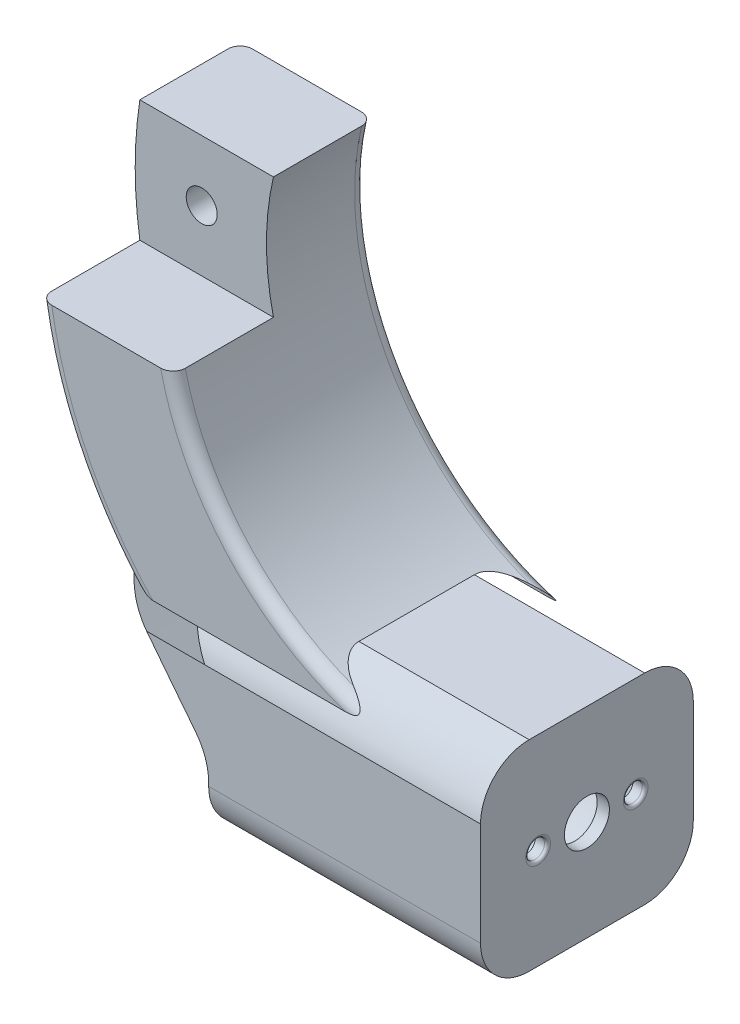
SolidWorks part; units mm, degrees
ref_plane "Front Plane" through (0, 0, 0) normal (0, 0, 1) x (1, 0, 0)
ref_plane "Top Plane" through (0, 0, 0) normal (0, 1, 0) x (1, 0, 0)
ref_plane "Right Plane" through (0, 0, 0) normal (1, 0, 0) x (0, 0, -1)
sketch "Sketch5" plane through (0, 0, -33) normal (0, 0, -1) x (-1, 0, 0)
  line L0 (31.0391, -85.25) -> (64.0391, -85.25)
  line L4 (54.5911, -55.6223) -> (76.5632, -55.6223)
  line L5 (76.5632, -35.6223) -> (54.5911, -35.6223)
  line L7 (76.5632, -35.6223) -> (54.5911, -35.6223)
  arc A0 (54.5911, -55.6223) -> (31.0391, -85.25) centre (11.6, -45.6223) cw
  arc A1 (76.5632, -55.6223) -> (64.0391, -85.25) centre (11.6, -45.6223) cw
  arc A4 (54.5911, -55.6223) -> (54.5911, -35.6223) centre (11.6, -45.6223) ccw
  arc A5 (76.5632, -55.6223) -> (76.5632, -35.6223) centre (11.6, -45.6223) ccw
  arc A6 (54.5911, -55.6223) -> (54.5911, -35.6223) centre (11.6, -45.6223) ccw
  arc A7 (76.5632, -55.6223) -> (76.5632, -35.6223) centre (11.6, -45.6223) ccw
  point P10 (21.6723, -47.1727)
  dimension "D1" = 0
  dimension "D2" = 33
extrude "Boss-Extrude1" add sketch "Sketch5" against normal blind 33
fillet "Fillet1" radius 2 4 edges at (-75.3303, -61.7053, -33) (-75.3303, -61.7053, 0) (-51.4762, -64.5465, 0) (-51.4762, -64.5465, -33)
sketch "Sketch6" plane through (0, 0, -16.5) normal (0, 0, -1) x (-1, 0, 0)
  line L2 (54.5911, -55.6223) -> (76.5632, -55.6223)
  line L3 (76.5632, -35.6223) -> (54.5911, -35.6223)
  line L4 (54.5911, -55.6223) -> (76.5632, -55.6223)
  line L5 (76.5632, -35.6223) -> (54.5911, -35.6223)
  arc A2 (54.5911, -55.6223) -> (54.5911, -35.6223) centre (11.6, -45.6223) ccw
  arc A3 (76.5632, -55.6223) -> (76.5632, -35.6223) centre (11.6, -45.6223) ccw
  arc A4 (54.5911, -55.6223) -> (54.5911, -35.6223) centre (11.6, -45.6223) ccw
  arc A5 (76.5632, -55.6223) -> (76.5632, -35.6223) centre (11.6, -45.6223) ccw
  dimension "D1" = 0
extrude "Cut-Extrude1" cut sketch "Sketch6" against normal through all
sketch "Sketch7" plane through (0, 0, -33) normal (0, 0, -1) x (-1, 0, 0)
  circle A0 centre (66.3894, -45.6223) radius 2.55 construction
  circle A1 centre (66.3894, -45.6223) radius 2.55
extrude "Cut-Extrude2" cut sketch "Sketch7" against normal through all
sketch "Sketch8" plane through (0, -85.25, 0) normal (0, -1, 0) x (1, 0, 0)
  line L0 (-31.0391, -16.5) -> (-64.0391, -16.5) construction
  line L2 (-5.0391, 1) -> (-80.0391, 1)
  line L3 (-5.0391, 1) -> (-5.0391, -34)
  line L4 (-64.0391, -2) -> (-64.0391, -31)
  line L5 (-61.5094, -33) -> (-35.2312, -33)
  line L6 (-31.0391, -31) -> (-31.0391, -2)
  line L7 (-35.2312, 0) -> (-61.5094, 0)
  line L8 (-64.0391, -2) -> (-64.0391, -31) construction
  line L9 (-61.5094, -33) -> (-35.2312, -33) construction
  line L10 (-31.0391, -31) -> (-31.0391, -2) construction
  line L11 (-35.2312, 0) -> (-61.5094, 0) construction
  line L12 (-5.0391, -34) -> (-80.0391, -34)
  line L13 (-80.0391, 1) -> (-80.0391, -34)
  line L14 (-5.0391, 1) -> (-80.0391, -34) construction
  line L15 (-5.0391, -34) -> (-80.0391, 1) construction
  spline S4 degree 3 poles (3861.8063, 733.6796) (237.2103, 60.9029) (-69.0926, -13.3538) (-63.9372, -31.5831) (-63.8768, -31.7218) (-63.7262, -31.9774) (-63.6343, -32.0975) (-63.4294, -32.3131) (-63.316, -32.4098) (-63.0712, -32.5821) (-62.9424, -32.6559) (-62.6737, -32.7823) (-62.5327, -32.835) (-38.7975, -39.736) (57.6195, 243.3563) (-4045.8809, -248.1128) knots -15.677405 -15.677405 -15.677405 -15.677405 0.125 0.125 0.25 0.25 0.375 0.375 0.5 0.5 0.625 0.625 0.75 0.75 21.415607 21.415607 21.415607 21.415607 only from (-64.0391, -31) to (-61.5094, -33)
  spline S5 degree 3 poles (-845.2917, 3882.356) (-204.2243, 391.8642) (-81.7875, -40.5827) (-33.5876, -32.8357) (-33.1862, -32.7392) (-32.5949, -32.5299) (-32.4012, -32.4496) (-32.0271, -32.2625) (-31.8461, -32.1554) (-31.5977, -31.9687) (-31.5185, -31.902) (-31.37, -31.756) (-31.2999, -31.6758) (-26.0157, -24.067) (-94.9331, 42.3352) (-3687.0514, -1649.0698) knots -29.123642 -29.123642 -29.123642 -29.123642 0.25 0.25 0.5 0.5 0.625 0.625 0.75 0.75 0.8125 0.8125 0.875 0.875 6.318151 6.318151 6.318151 6.318151 only from (-35.2312, -33) to (-31.0391, -31)
  spline S6 degree 3 poles (-3746.2688, 1475.8653) (-97.1676, -74.575) (-25.9769, -9.0228) (-31.2979, -1.3268) (-31.3675, -1.2467) (-31.5159, -1.1002) (-31.5955, -1.033) (-31.8461, -0.8444) (-32.0274, -0.7374) (-32.3984, -0.5516) (-32.5901, -0.472) (-32.9827, -0.3326) (-33.1837, -0.2731) (-33.5864, -0.1729) (-33.7891, -0.1319) (-84.583, 8.0412) (-208.7708, -478.706) (-773.7407, -3929.361) knots -5.392416 -5.392416 -5.392416 -5.392416 0.125 0.125 0.1875 0.1875 0.25 0.25 0.375 0.375 0.5 0.5 0.625 0.625 0.75 0.75 31.758712 31.758712 31.758712 31.758712 only from (-31.0391, -2) to (-35.2312, 0)
  spline S7 degree 3 poles (-587.6612, 3963.4932) (118.6266, -657.2905) (-26.4558, 10.2926) (-62.5307, -0.1643) (-62.6715, -0.2169) (-62.9397, -0.3427) (-63.0683, -0.4161) (-63.3126, -0.5875) (-63.4272, -0.6849) (-63.6318, -0.8995) (-63.7238, -1.0191) (-63.8758, -1.276) (-63.9354, -1.412) (-68.4766, -17.3285) (164.3416, -85.7017) (2504.2589, 3054.3214) knots -31.157923 -31.157923 -31.157923 -31.157923 0.25 0.25 0.375 0.375 0.5 0.5 0.625 0.625 0.75 0.75 0.875 0.875 14.534731 14.534731 14.534731 14.534731 only from (-61.5094, 0) to (-64.0391, -2)
  spline S8 degree 3 poles (-64.0391, -31) (-64.0391, -31.1504) (-64.0181, -31.2969) (-63.9372, -31.5831) (-63.8768, -31.7218) (-63.7262, -31.9774) (-63.6343, -32.0975) (-63.4294, -32.3131) (-63.316, -32.4098) (-63.0712, -32.5821) (-62.9424, -32.6559) (-62.6737, -32.7823) (-62.5327, -32.835) (-62.1046, -32.9595) (-61.8085, -33) (-61.5094, -33) knots 0 0 0 0 0.125 0.125 0.25 0.25 0.375 0.375 0.5 0.5 0.625 0.625 0.75 0.75 1 1 1 1 construction
  spline S9 degree 3 poles (-35.2312, -33) (-34.8134, -33) (-34.4012, -32.9665) (-33.5876, -32.8357) (-33.1862, -32.7392) (-32.5949, -32.5299) (-32.4012, -32.4496) (-32.0271, -32.2625) (-31.8461, -32.1554) (-31.5977, -31.9687) (-31.5185, -31.902) (-31.37, -31.756) (-31.2999, -31.6758) (-31.12, -31.4167) (-31.0391, -31.2129) (-31.0391, -31) knots 0 0 0 0 0.25 0.25 0.5 0.5 0.625 0.625 0.75 0.75 0.8125 0.8125 0.875 0.875 1 1 1 1 construction
  spline S10 degree 3 poles (-31.0391, -2) (-31.0391, -1.7876) (-31.1191, -1.5854) (-31.2979, -1.3268) (-31.3675, -1.2467) (-31.5159, -1.1002) (-31.5955, -1.033) (-31.8461, -0.8444) (-32.0274, -0.7374) (-32.3984, -0.5516) (-32.5901, -0.472) (-32.9827, -0.3326) (-33.1837, -0.2731) (-33.5864, -0.1729) (-33.7891, -0.1319) (-34.4009, -0.0335) (-34.8136, 0) (-35.2312, 0) knots 0 0 0 0 0.125 0.125 0.1875 0.1875 0.25 0.25 0.375 0.375 0.5 0.5 0.625 0.625 0.75 0.75 1 1 1 1 construction
  spline S11 degree 3 poles (-61.5094, 0) (-61.8087, 0) (-62.1017, -0.0399) (-62.5307, -0.1643) (-62.6715, -0.2169) (-62.9397, -0.3427) (-63.0683, -0.4161) (-63.3126, -0.5875) (-63.4272, -0.6849) (-63.6318, -0.8995) (-63.7238, -1.0191) (-63.8758, -1.276) (-63.9354, -1.412) (-64.0178, -1.7006) (-64.0391, -1.8494) (-64.0391, -2) knots 0 0 0 0 0.25 0.25 0.375 0.375 0.5 0.5 0.625 0.625 0.75 0.75 0.875 0.875 1 1 1 1 construction
  point P6 (-47.5391, -16.5)
  point P8 (-42.5391, -16.5)
  dimension "D2" = 5
  dimension "D3" = 35
  dimension "D4" = 75
  dimension "D1" = 0
extrude "Boss-Extrude2" add sketch "Sketch8" along normal blind 33
sketch "Sketch9" plane through (-5.0391, 0, 0) normal (1, 0, 0) x (0, 0, -1)
  line L0 (16.5, -85.25) -> (16.5, -118.25) construction
  line L1 (-1, -101.75) -> (34, -101.75) construction
  line L4 (34, -85.25) -> (-1, -85.25)
  line L5 (-1, -85.25) -> (-1, -118.25)
  line L6 (-1, -118.25) -> (34, -118.25)
  line L7 (34, -118.25) -> (34, -85.25)
  line L8 (34, -85.25) -> (-1, -85.25) construction
  line L9 (-1, -85.25) -> (-1, -118.25) construction
  line L10 (-1, -118.25) -> (34, -118.25) construction
  line L11 (34, -118.25) -> (34, -85.25) construction
  circle A0 centre (16.5, -101.75) radius 12.55
  dimension "D2" = 25.1
  dimension "D1" = 0
extrude "Cut-Extrude3" cut sketch "Sketch9" against normal through all
fillet "Fillet2" radius 8 4 edges at (-42.5391, -118.25, 1) (-42.5391, -85.25, 1) (-42.5391, -118.25, -34) (-42.5391, -85.25, -34)
sketch "Sketch10" plane through (-5.0391, 0, 0) normal (1, 0, 0) x (0, 0, -1)
  line L0 (16.5, -118.25) -> (16.5, -85.25) construction
  line L1 (13, -101.75) -> (3.95, -101.75) construction
  line L4 (-1, -93.25) -> (-1, -110.25)
  line L5 (7, -118.25) -> (26, -118.25)
  line L6 (34, -110.25) -> (34, -93.25)
  line L7 (26, -85.25) -> (7, -85.25)
  line L8 (-1, -93.25) -> (-1, -110.25)
  line L9 (7, -118.25) -> (26, -118.25)
  line L10 (34, -110.25) -> (34, -93.25)
  line L11 (26, -85.25) -> (7, -85.25)
  circle A0 centre (8.475, -101.75) radius 1.55
  circle A1 centre (24.525, -101.75) radius 1.55
  circle A2 centre (16.5, -101.75) radius 3.5 construction
  circle A3 centre (16.5, -101.75) radius 12.55 construction
  arc A4 (-1, -110.25) -> (7, -118.25) centre (7, -110.25) ccw
  arc A5 (26, -118.25) -> (34, -110.25) centre (26, -110.25) ccw
  arc A6 (34, -93.25) -> (26, -85.25) centre (26, -93.25) ccw
  arc A7 (7, -85.25) -> (-1, -93.25) centre (7, -93.25) ccw
  arc A8 (-1, -110.25) -> (7, -118.25) centre (7, -110.25) ccw
  arc A9 (26, -118.25) -> (34, -110.25) centre (26, -110.25) ccw
  arc A10 (34, -93.25) -> (26, -85.25) centre (26, -93.25) ccw
  arc A11 (7, -85.25) -> (-1, -93.25) centre (7, -93.25) ccw
  circle A12 centre (16.5, -101.75) radius 3.7
  circle A13 centre (16.5, -101.75) radius 3.5 construction
  point P22 (0, 0)
  point P23 (8.475, -101.75)
  point P24 (13, -101.75)
  dimension "D2" = 3.1
  dimension "D3" = 7
  dimension "D4" = 7.4
  dimension "D1" = 0
extrude "Boss-Extrude3" add sketch "Sketch10" along normal blind 2
fillet "Fillet3" radius 0.5 2 edges at (-3.0391, -101.75, -22.975) (-3.0391, -101.75, -10.025)
sketch "Sketch12" plane through (0, 0, -33) normal (0, 0, -1) x (-1, 0, 0)
  line L0 (80.0391, -118.25) -> (3.0391, -118.25) construction
  line L1 (80.0391, -118.25) -> (80.0391, -110.25) construction
  line L6 (80.0391, -110.25) -> (80.0391, -93.25) construction
  line L7 (80.0391, -93.25) -> (80.0391, -85.25) construction
  line L8 (64.0391, -85.25) -> (80.0391, -85.25) construction
  line L9 (80.0391, -118.25) -> (38.0391, -118.25) construction
  line L10 (80.0391, -118.25) -> (80.0391, -110.25)
  line L11 (80.0391, -110.25) -> (80.0391, -93.25)
  line L12 (80.0391, -93.25) -> (80.0391, -85.25)
  line L13 (64.0391, -85.25) -> (80.0391, -85.25)
  line L14 (47.7444, -106.25) -> (47.7444, -118.25)
  line L15 (47.7444, -118.25) -> (80.0391, -118.25)
  arc A0 (62.6655, -87.005) -> (76.5632, -35.6223) centre (11.6, -45.6223) ccw construction
  arc A1 (62.6655, -87.005) -> (76.5632, -35.6223) centre (11.6, -45.6223) ccw construction
  arc A7 (64.0391, -85.25) -> (38.0391, -118.25) centre (-766.7789, 542.5915) cw construction
  arc A8 (47.7444, -106.25) -> (64.0391, -85.25) centre (-766.7789, 542.5915) ccw
  dimension "D1" = 35
  dimension "D2" = 12
extrude "Cut-Extrude4" cut sketch "Sketch12" against normal through all both and the other way through all
fillet "Fillet6" radius 10 2 edges at (-47.7444, -106.25, -1.8923) (-47.7444, -106.25, -31.1077)
fillet "Fillet8" radius 3 1 edges at (-47.7444, -118.25, -16.5) tangent propagation no
